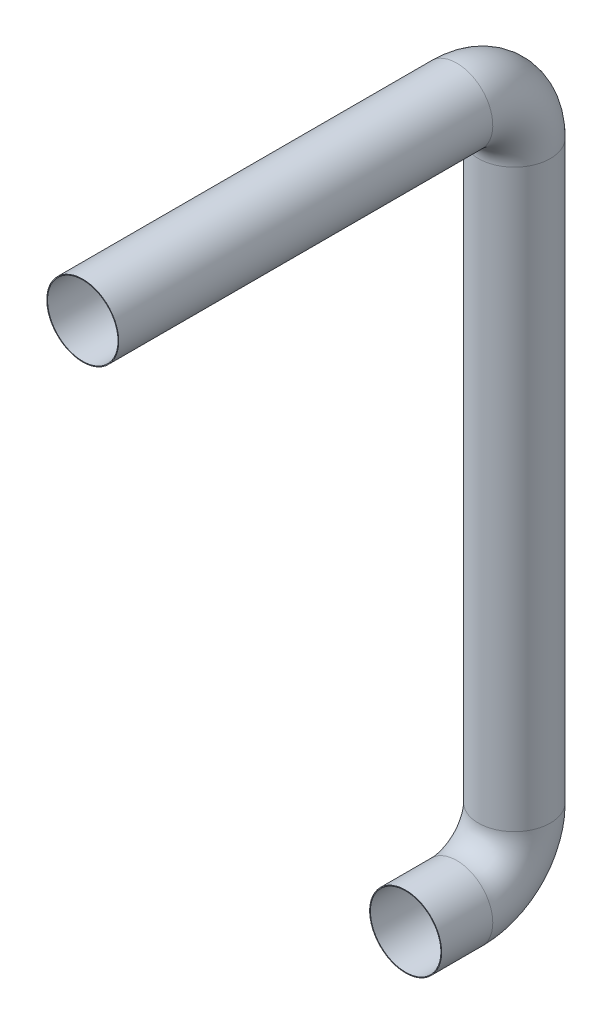
SolidWorks part; units mm, degrees
material "AISI 316 Stainless Steel Sheet (SS)"
ref_plane "Front Plane" through (0, 0, 0) normal (0, 0, 1) x (1, 0, 0)
ref_plane "Top Plane" through (0, 0, 0) normal (0, 1, 0) x (1, 0, 0)
ref_plane "Right Plane" through (0, 0, 0) normal (1, 0, 0) x (0, 0, -1)
sketch "Sketch31" plane through (0, 0, 0) normal (0, 0, 1) x (1, 0, 0)
  circle A0 centre (0, 0) radius 24.5
  circle A1 centre (0, 0) radius 25
  dimension "D1" = 50
  dimension "D2" = 0.5
sketch "Sketch3" plane through (0, 0, 0) normal (1, 0, 0) x (0, 0, -1)
  line L0 (0, 0) -> (260, 0)
  line L1 (300, -40) -> (300, -440)
  line L2 (260, -480) -> (224.43, -480)
  arc A0 (260, 0) -> (300, -40) centre (260, -40) cw
  arc A1 (300, -440) -> (260, -480) centre (260, -440) cw
  dimension "D1" = 300
  dimension "D3" = 40
  dimension "D2" = 400
  dimension "D4" = 35.57
sweep "Sweep1" add profiles "Sketch31" path "Sketch3"
